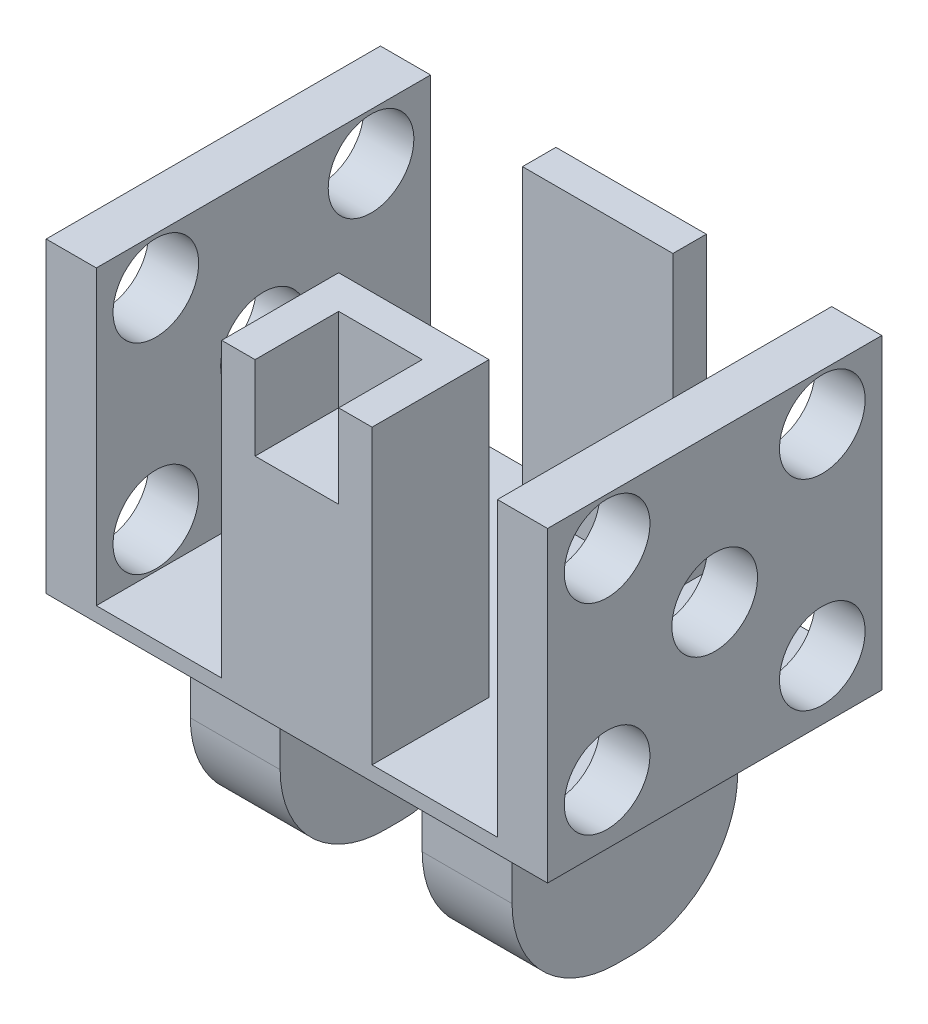
SolidWorks part; units mm, degrees
ref_plane "Front Plane" through (0, 0, 0) normal (0, 0, 1) x (1, 0, 0)
ref_plane "Top Plane" through (0, 0, 0) normal (0, 1, 0) x (1, 0, 0)
ref_plane "Right Plane" through (0, 0, 0) normal (1, 0, 0) x (0, 0, -1)
sketch "Sketch1" plane through (0, 0, 0) normal (0, 0, 1) x (1, 0, 0)
  line L1 (-60, 60) -> (60, 60)
  line L2 (-60, 60) -> (-60, -60)
  line L3 (-60, -60) -> (60, -60)
  line L4 (60, 60) -> (60, -60)
  line L5 (-60, 60) -> (60, -60) construction
  line L6 (-60, -60) -> (60, 60) construction
  line L7 (17, -60) -> (-17, -60)
  line L8 (17, -60) -> (17, -13.5)
  line L9 (17, -13.5) -> (-17, -13.5)
  line L10 (-17, -60) -> (-17, -13.5)
  point P0 (0, 0)
  dimension "D1" = 120
  dimension "D2" = 120
  dimension "D3" = 46.5
  dimension "D4" = 34
  dimension "D5" = 43
extrude "Boss-Extrude1" add sketch "Sketch1" along normal blind 54 contours L3 L10 L9 L8 L4 L1 L2 region at (0, 4.5325, 0)
sketch "Sketch2" plane through (60, 0, 0) normal (1, 0, 0) x (0, 0, -1)
  line L0 (-54, -13.5) -> (0, -13.5) construction
  circle A0 centre (-27, -24.75) radius 10.25
  dimension "D1" = 11.25
extrude "Cut-Extrude1" cut sketch "Sketch2" against normal through all both and the other way through all
sketch "Sketch3" plane through (60, 0, 0) normal (1, 0, 0) x (0, 0, -1)
  line L0 (-54, 60) -> (0, 60) construction
  circle A0 centre (-27, 24.75) radius 10.25
  dimension "D1" = 35.25
extrude "Cut-Extrude2" cut sketch "Sketch3" against normal through all both and the other way through all
sketch "Sketch4" plane through (0, 0, 54) normal (0, 0, 1) x (1, 0, 0)
  line L1 (-60, -60) -> (-38.5, -60)
  line L2 (-60, -60) -> (-60, -13.5)
  line L3 (-60, -13.5) -> (-38.5, -13.5)
  line L4 (-38.5, -60) -> (-38.5, -13.5)
  line L5 (60, -60) -> (38.5, -60)
  line L6 (60, -60) -> (60, -13.5)
  line L7 (60, -13.5) -> (38.5, -13.5)
  line L8 (38.5, -60) -> (38.5, -13.5)
  dimension "D1" = 46.5
  dimension "D2" = 46.5
extrude "Cut-Extrude3" cut sketch "Sketch4" against normal through all both and the other way through all
fillet "Fillet1" radius 25 4 edges at (-27.75, -60, 54) (-27.75, -60, 0) (27.75, -60, 0) (27.75, -60, 54)
sketch "Sketch5" plane through (0, 60, 0) normal (0, 1, 0) x (1, 0, 0)
  line L1 (60, 0) -> (-60, 0)
  line L2 (60, 0) -> (60, 13)
  line L3 (60, 13) -> (-60, 13)
  line L4 (-60, 0) -> (-60, 13)
  line L5 (-60, -54) -> (60, -54)
  line L6 (-60, -54) -> (-60, -67)
  line L7 (-60, -67) -> (60, -67)
  line L8 (60, -54) -> (60, -67)
  dimension "D1" = 13
  dimension "D2" = 13
extrude "Boss-Extrude2" add sketch "Sketch5" against normal blind 73.5
sketch "Sketch6" plane through (0, 60, 0) normal (0, 1, 0) x (1, 0, 0)
  line L0 (60, 13) -> (-60, 13) construction
  line L1 (-48, 13) -> (-18, 13)
  line L2 (-48, 13) -> (-48, -67)
  line L3 (-48, -67) -> (-18, -67)
  line L4 (-18, 13) -> (-18, -67)
  line L5 (-60, -67) -> (60, -67) construction
  line L6 (-60, -67) -> (-60, 13) construction
  line L11 (0, 0) -> (0, 35.5501) construction
  line L12 (18, 13) -> (18, -67)
  line L13 (48, -67) -> (18, -67)
  line L14 (48, 13) -> (48, -67)
  line L15 (48, 13) -> (18, 13)
  dimension "D1" = 12
  dimension "D2" = 30
extrude "Cut-Extrude4" cut sketch "Sketch6" against normal blind 70
sketch "Sketch8" plane through (60, 0, 0) normal (1, 0, 0) x (0, 0, -1)
  line L0 (-27, 24.75) -> (-27, 48.4608) construction
  line L1 (-27, 48.4608) -> (-27, 24.75) construction
  line L2 (-27, 24.75) -> (-1.6977, 24.75) construction
  line L3 (-67, 60) -> (13, 60) construction
  line L4 (-67, -13.5) -> (-67, 60) construction
  circle A0 centre (-52.75, 48.75) radius 10.25
  circle A1 centre (-1.25, 48.75) radius 10.25
  circle A2 centre (-1.25, 0.75) radius 10.25
  circle A3 centre (-52.75, 0.75) radius 10.25
  dimension "D1" = 11.25
  dimension "D2" = 20.5
  dimension "D3" = 14.25
extrude "Cut-Extrude6" cut sketch "Sketch8" against normal blind 20
sketch "Sketch9" plane through (0, 0, 67) normal (0, 0, 1) x (1, 0, 0)
  line L0 (-18, 60) -> (18, 60) construction
  line L1 (-10, 60) -> (10, 60)
  line L2 (-10, 60) -> (-10, 40)
  line L3 (-10, 40) -> (10, 40)
  line L4 (10, 60) -> (10, 40)
  line L5 (-18, -10) -> (-18, 60) construction
  dimension "D1" = 20
  dimension "D2" = 8
  dimension "D3" = 20
extrude "Cut-Extrude7" cut sketch "Sketch9" against normal blind 20
ref_plane "Plane1" through (0, 0, 0) normal (1, 0, 0) x (0, 0, -1)
mirror "Mirror1" about plane through (0, 0, 0) normal (1, 0, 0) of "Cut-Extrude6"
sketch "Sketch10" plane through (0, 60, 0) normal (0, 1, 0) x (1, 0, 0)
  line L0 (-18, -67) -> (-18, 13) construction
  line L1 (-18, -39) -> (18, -39)
  line L2 (-18, -39) -> (-18, 5)
  line L3 (-18, 5) -> (18, 5)
  line L4 (18, -39) -> (18, 5)
  line L5 (18, 13) -> (18, -67) construction
  line L7 (-10, -47) -> (10, -47) construction
  line L8 (18, 13) -> (-18, 13) construction
  dimension "D1" = 8
  dimension "D2" = 8
extrude "Cut-Extrude8" cut sketch "Sketch10" against normal blind 70
